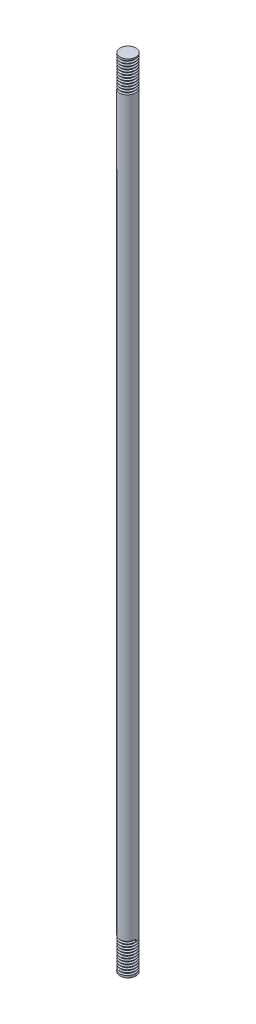
SolidWorks part; units mm, degrees
ref_plane "Front Plane" through (0, 0, 0) normal (0, 0, 1) x (1, 0, 0)
ref_plane "Top Plane" through (0, 0, 0) normal (0, 1, 0) x (1, 0, 0)
ref_plane "Right Plane" through (0, 0, 0) normal (1, 0, 0) x (0, 0, -1)
sketch "Sketch1" plane through (0, 0, 0) normal (0, 1, 0) x (1, 0, 0)
  circle A0 centre (0, 0) radius 4
  dimension "D1" = 8
extrude "Boss-Extrude1" add sketch "Sketch1" along normal blind 400
thread "Thread1" pitch 1.25 method cut profile "Thread Profile2" start angle 0, offset 0, length 15, pitch 1.25, diameter 8
ref_plane "Plane2" through (-4, 400, 0) normal (0, 0, 1) x (-1, 0, 0)
sketch "Thread Profile2" plane through (-4, 400, 0) normal (0, 0, 1) x (-1, 0, 0)
  line L0 (0, 0) -> (0, 1.25) construction
  line L11 (0, 0) -> (0, 1.0937)
  line L12 (0, 1.0937) -> (-0.6766, 0.7031)
  line L13 (-0.6766, 0.7031) -> (-0.6766, 0.3906)
  line L15 (-0.6766, 0.3906) -> (0, 0)
  line L17 (-0.6766, 0.5469) -> (0, 0.5469) construction
  point P2 (0, 0)
  dimension "Pitch" = 1.25
  dimension "Profile_Angle" = 60
  dimension "Profile_Land" = 0.3125
  dimension "Profile_Height" = 0.6766
thread "Thread2" pitch 1.25 method cut profile "Thread Profile3" start angle 0, offset 0, length 15, pitch 1.25, diameter 8
ref_plane "Plane3" through (4, 0, 0) normal (0, 0, 1) x (1, 0, 0)
sketch "Thread Profile3" plane through (4, 0, 0) normal (0, 0, 1) x (1, 0, 0)
  line L0 (0, 0) -> (0, 1.25) construction
  line L11 (0, 0) -> (0, 1.0937)
  line L12 (0, 1.0937) -> (-0.6766, 0.7031)
  line L13 (-0.6766, 0.7031) -> (-0.6766, 0.3906)
  line L15 (-0.6766, 0.3906) -> (0, 0)
  line L17 (-0.6766, 0.5469) -> (0, 0.5469) construction
  point P2 (0, 0)
  dimension "Pitch" = 1.25
  dimension "Profile_Angle" = 60
  dimension "Profile_Land" = 0.3125
  dimension "Profile_Height" = 0.6766
